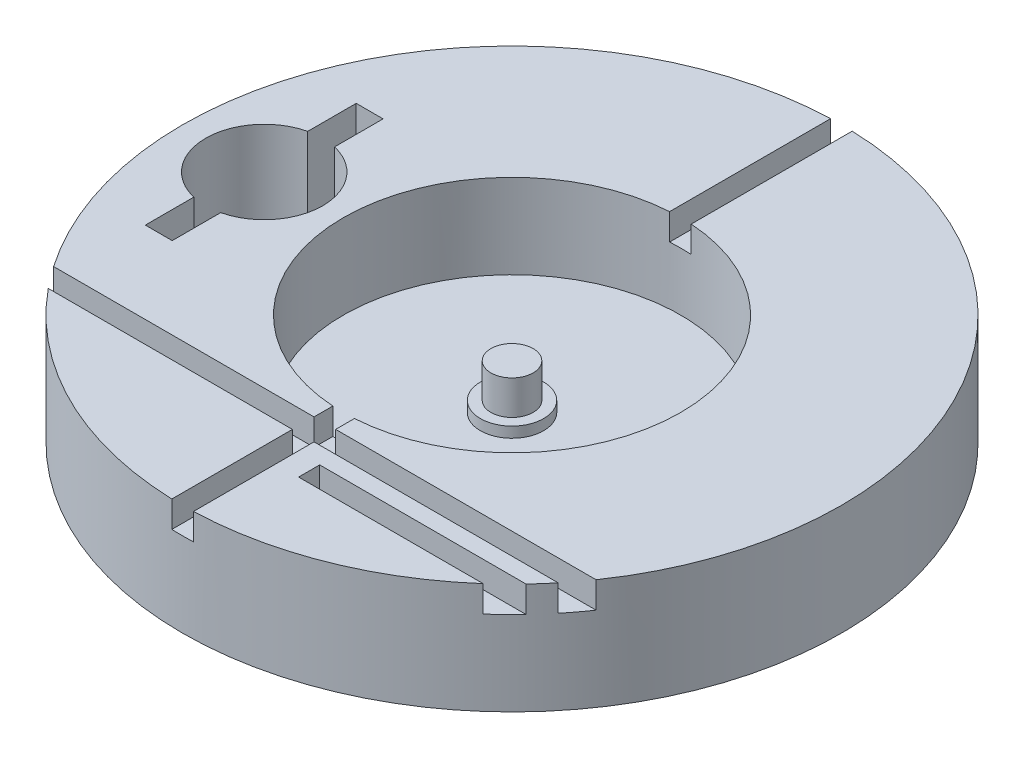
SolidWorks part; units mm, degrees
material "Cast Alloy Steel"
ref_plane "Front Plane" through (0, 0, 0) normal (0, 0, 1) x (1, 0, 0)
ref_plane "Top Plane" through (0, 0, 0) normal (0, 1, 0) x (1, 0, 0)
ref_plane "Right Plane" through (0, 0, 0) normal (1, 0, 0) x (0, 0, -1)
sketch "Sketch1" plane through (0, 0, 0) normal (0, 1, 0) x (1, 0, 0)
  circle A0 centre (0, 0) radius 62.5
  dimension "D1" = 125
extrude "Boss-Extrude1" add sketch "Sketch1" along normal blind 21
sketch "Sketch2" plane through (0, 21, 0) normal (0, 1, 0) x (1, 0, 0)
  circle A0 centre (0, 0) radius 32
  circle A1 centre (0, 0) radius 6
  dimension "D1" = 64
extrude "Cut-Extrude1" cut sketch "Sketch2" against normal blind 16
sketch "Sketch3" plane through (0, 21, 0) normal (0, 1, 0) x (1, 0, 0)
  circle A0 centre (0, 0) radius 6
  circle A1 centre (0, 0) radius 4
extrude "Cut-Extrude2" cut sketch "Sketch3" against normal blind 14
sketch "Sketch4" plane through (0, 21, 0) normal (0, 1, 0) x (1, 0, 0)
  circle A0 centre (0, 0) radius 4
extrude "Cut-Extrude3" cut sketch "Sketch4" against normal blind 7.5
sketch "Sketch5" plane through (0, 21, 0) normal (0, 1, 0) x (1, 0, 0)
  line L0 (0, 0) -> (2.05, 0) construction
  line L1 (0, 0) -> (-2.05, 0) construction
  line L2 (2.05, 62.4664) -> (2.05, -62.4664)
  line L3 (-2.05, 62.4664) -> (-2.05, -62.4664)
  circle A0 centre (0, 0) radius 62.5 construction
  arc A1 (-2.05, -62.4664) -> (2.05, -62.4664) centre (0, 0) ccw
  arc A2 (2.05, 62.4664) -> (-2.05, 62.4664) centre (0, 0) ccw
  dimension "D1" = 2.05
  dimension "D2" = 2.05
extrude "Cut-Extrude4" cut sketch "Sketch5" against normal blind 5
sketch "Sketch6" plane through (0, 21, 0) normal (0, 1, 0) x (1, 0, 0)
  line L0 (0, 0) -> (0, -37.5) construction
  line L2 (-48.35, -39.6046) -> (48.35, -39.6046)
  line L4 (-51.4393, -35.5) -> (51.4393, -35.5)
  line L6 (-48.5276, -39.3868) -> (51.4393, -35.5) construction
  line L7 (-51.4393, -35.5) -> (48.5276, -39.3868) construction
  arc A0 (2.05, -62.4664) -> (2.05, 62.4664) centre (0, 0) ccw construction
  arc A1 (-51.4393, -35.5) -> (-48.35, -39.6046) centre (0, 0) ccw
  arc A2 (48.35, -39.6046) -> (51.4393, -35.5) centre (0, 0) ccw
  dimension "D1" = 37.5
  dimension "D2" = 96.7
  dimension "D3" = 102.8786
extrude "Cut-Extrude5" cut sketch "Sketch6" against normal blind 5
sketch "Sketch9" plane through (0, 21, 0) normal (0, 1, 0) x (1, 0, 0)
  line L0 (0, 0) -> (0, -45) construction
  line L1 (0, -45) -> (43.3734, -45) construction
  line L2 (47.1162, -42.8483) -> (45.5003, -42.8483)
  line L3 (6.3701, -42.8483) -> (47.1162, -42.8483)
  line L4 (6.3701, -42.8483) -> (6.3701, -46.8483)
  line L5 (6.3701, -46.8483) -> (41.3701, -46.8483)
  line L6 (41.3701, -45) -> (41.3701, -46.8483)
  line L7 (6.3701, -42.8483) -> (41.3701, -46.8483) construction
  line L8 (6.3701, -46.8483) -> (47.1162, -42.8483) construction
  arc A0 (41.3701, -46.8483) -> (45.5003, -42.8483) centre (0, 0) ccw
  arc A1 (2.05, -62.4664) -> (48.35, -39.6046) centre (0, 0) ccw construction
  point P3 (25.1977, -45)
  arc M7 (2.05, -62.4664) -> (48.35, -39.6046) centre (0, 0) ccw
  dimension "D1" = 45
  dimension "D2" = 35
  dimension "D3" = 4
  dimension "D4" = 25.1977
extrude "Cut-Extrude6" cut sketch "Sketch9" against normal blind 5 contours L4 L5 L2 L3 M7 region at (24.9535, 21, 44.8112)
sketch "Sketch10" plane through (0, 21, 0) normal (0, 1, 0) x (1, 0, 0)
  line L0 (0, 0) -> (-47, 0) construction
  line L1 (-49.55, 10.8031) -> (-49.55, 20)
  line L2 (-49.55, -20) -> (-44.45, -20)
  line L3 (-49.55, -20) -> (-49.55, -10.8031)
  line L4 (-49.55, 20) -> (-44.45, 20)
  line L5 (-44.45, -20) -> (-44.45, -10.8031)
  line L6 (-49.55, -20) -> (-44.45, 20) construction
  line L7 (-49.55, 20) -> (-44.45, -20) construction
  line L8 (-44.45, 10.8031) -> (-44.45, 20)
  arc A0 (-49.55, 10.8031) -> (-49.55, -10.8031) centre (-47, 0) ccw
  arc A1 (-44.45, -10.8031) -> (-44.45, 10.8031) centre (-47, 0) ccw
  dimension "D1" = 47
  dimension "D2" = 22.2
  dimension "D3" = 40
  dimension "D4" = 5.1
extrude "Cut-Extrude7" cut sketch "Sketch10" against normal blind 18.5
